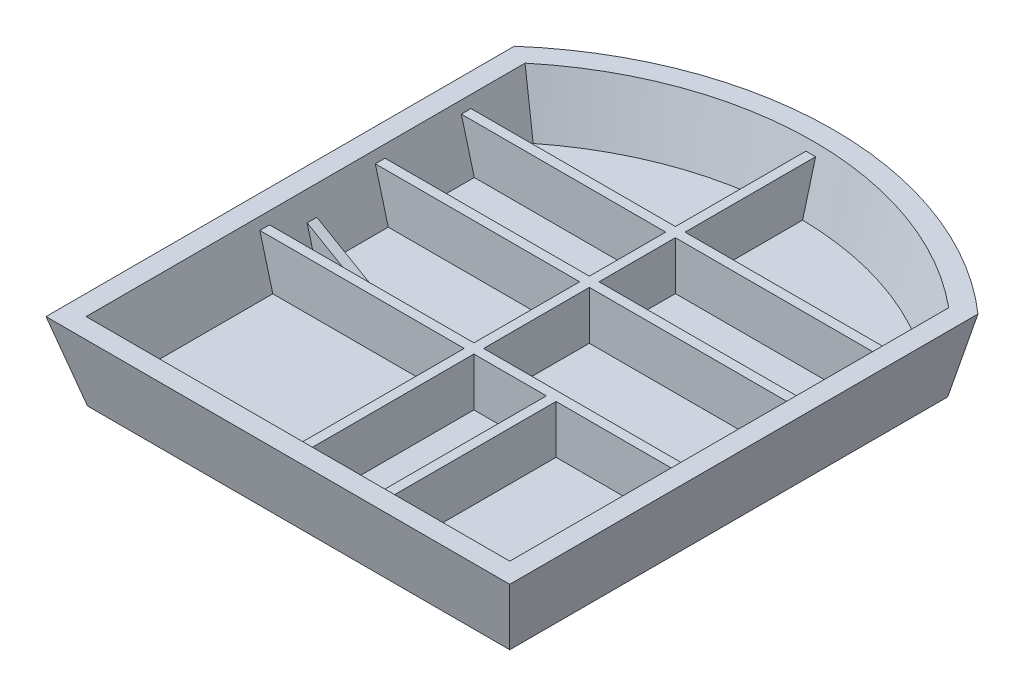
SolidWorks part; units mm, degrees
material "AISI 1020"
ref_plane "Front Plane" through (0, 0, 0) normal (0, 0, 1) x (1, 0, 0)
ref_plane "Top Plane" through (0, 0, 0) normal (0, 1, 0) x (1, 0, 0)
ref_plane "Right Plane" through (0, 0, 0) normal (1, 0, 0) x (0, 0, -1)
sketch "Sketch1" plane through (0, 0, 0) normal (0, 1, 0) x (1, 0, 0)
  line L1 (-109.0299, -113.0819) -> (109.0299, -113.0819)
  line L2 (-109.0299, -113.0819) -> (-109.0299, 113.0819)
  line L3 (-109.0299, 113.0819) -> (109.0299, 113.0819) construction
  line L4 (109.0299, -113.0819) -> (109.0299, 113.0819)
  line L5 (-109.0299, -113.0819) -> (109.0299, 113.0819) construction
  line L6 (-109.0299, 113.0819) -> (109.0299, -113.0819) construction
  arc A0 (-109.0299, 113.0819) -> (109.0299, 113.0819) centre (0, -18.4239) cw
  point P0 (0, 0)
extrude "Boss-Extrude1" add sketch "Sketch1" along normal blind 40 draft 15 draft outward yes
shell "Shell1" thickness 10 removed face at (0, 40, -8.3863)
ref_plane "Plane1" through (0, 35, 0) normal (0, 1, 0) x (1, 0, 0)
sketch "Sketch5" plane through (0, 35, 0) normal (0, 1, 0) x (1, 0, 0)
  line L0 (0, 85.907) -> (0, -50.5491)
  line L1 (-35.2145, -22.5576) -> (48.8201, -22.5576)
  line L2 (-27.2112, 37.0669) -> (32.8135, 37.0669)
  line L3 (-35.2145, 81.4851) -> (36.415, 81.4851)
rib "Rib7" sketch "Sketch5" sketch "Sketch5" thickness 5 extrusion direction normal to sketch draft on no parameters "D1"=5
sketch "Sketch6" plane through (0, 35, 0) normal (0, 1, 0) x (1, 0, 0)
  line L0 (42.4174, -43.3661) -> (42.4174, -74.9791)
rib "Rib8" sketch "Sketch6" sketch "Sketch6" thickness 5 extrusion direction normal to sketch draft on no parameters "D1"=5
sketch "Sketch7" plane through (0, 0, 0) normal (0, 0, 1) x (1, 0, 0)
  line L0 (-101.5408, 25.3621) -> (-83.2783, 14.8182)
  line L1 (-101.3566, 10) -> (-2.5, 10) construction
  dimension "D1" = 30
rib "Rib9" sketch "Sketch7" sketch "Sketch7" thickness 5 extrusion direction parallel to sketch draft on no parameters "D1"=5
